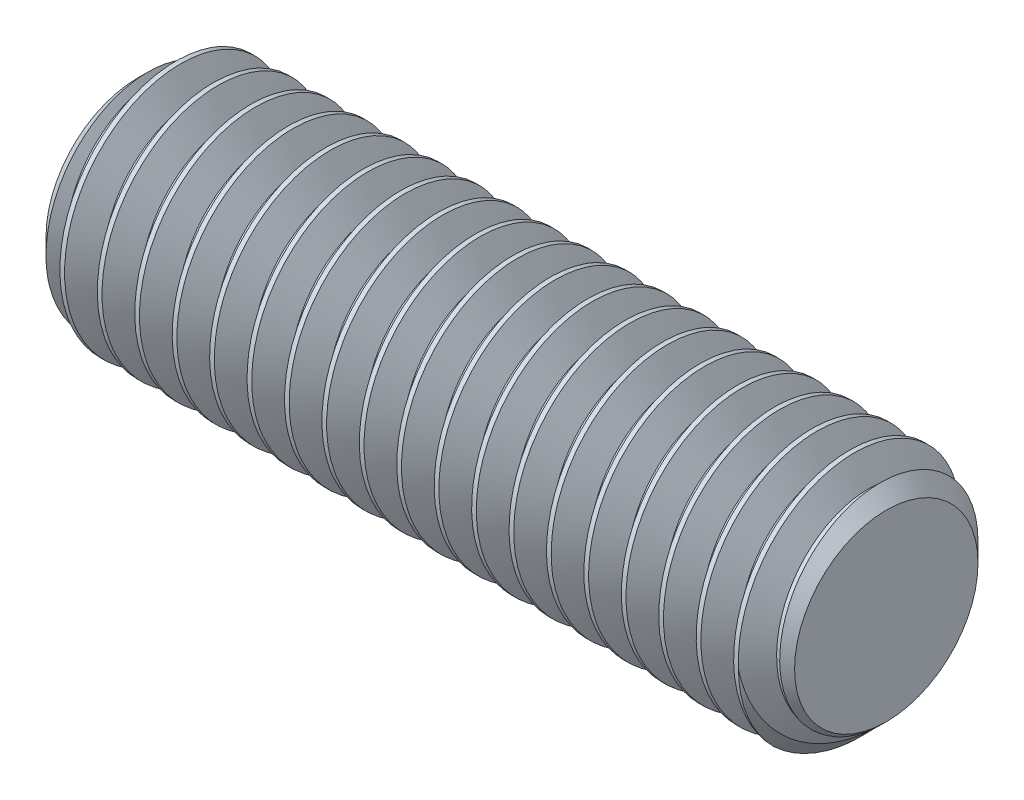
SolidWorks part; units mm, degrees
ref_plane "Front Plane" through (0, 0, 0) normal (0, 0, 1) x (1, 0, 0)
ref_plane "Top Plane" through (0, 0, 0) normal (0, 1, 0) x (1, 0, 0)
ref_plane "Right Plane" through (0, 0, 0) normal (1, 0, 0) x (0, 0, -1)
sketch "Sketch1" plane through (0, 0, 0) normal (0, 0, 1) x (1, 0, 0)
  line L0 (-12.5, 0) -> (12.5, 0) construction
  line L1 (12.5, 4) -> (12.5, -4) construction
  line L2 (-12.5, 4) -> (-12.5, -4) construction
  point P6 (8.125, -4)
  dimension "D1" = 4.375
  dimension "Thread Diameter" = 8
  dimension "Length" = 25
sketch "Sketch2" plane through (0, 0, 0) normal (1, 0, 0) x (0, 0, -1)
  circle A0 centre (0, 0) radius 4
extrude "Boss-Extrude1" add sketch "Sketch2" against normal up to vertex (12.5 mm away) and the other way up to vertex (12.5 mm away) up to point (-12.5, 0, 0) other way up to point (12.5, 0, 0)
sketch "Sketch3" plane through (12.5, 0, 0) normal (1, 0, 0) x (0, 0, -1)
  circle A1 centre (0, 0) radius 4
  circle A2 centre (0, 0) radius 4
  dimension "D1" = 0
curve "Helix/Spiral1" pitch 1.25 height 26.25 turns 21 parameters "Pitch"=1.25
chamfer "Chamfer1" distance 0.9375 angle 45 2 edges at (-12.5, 0, -4) (12.5, 0, -4)
sketch "Sketch4" plane through (0, 0, 0) normal (0, 0, 1) x (1, 0, 0)
  line L0 (12.4219, 4.1353) -> (13.0469, 3.0528) construction
  line L1 (13.0469, 3.0528) -> (13.6719, 4.1353) construction
  line L2 (13.6719, 4.1353) -> (12.4219, 4.1353) construction
  line L3 (13.0469, 4.1353) -> (13.0469, 4) construction
  line L4 (13.0469, 3.0528) -> (13.0469, 3.1881) construction
  line L5 (12.9687, 3.1881) -> (13.125, 3.1881) construction
  line L6 (12.5, 4) -> (13.5937, 4) construction
  line L7 (12.9687, 3.1881) -> (12.4609, 4.0677)
  line L8 (12.9687, 3.1881) -> (13.125, 3.1881)
  line L9 (12.4609, 4.0677) -> (13.6328, 4.0677)
  line L10 (13.6328, 4.0677) -> (13.125, 3.1881)
  point P13 (13.0469, 4.0677)
  dimension "D1" = 1.25
  dimension "D2" = 0.1562
sweep "Cut-Sweep3" cut profiles "Sketch4" path "Helix/Spiral1"
equation "\"D3@Helix/Spiral1\" = \"Length@Sketch1\"+\"Pitch@Helix/Spiral1\""
equation "\"D1@Chamfer1\" = \"Pitch@Helix/Spiral1\"*.75"
equation "\"D1@Sketch4\" = \"Pitch@Helix/Spiral1\""
equation "\"D2@Sketch4\" = \"D1@Sketch4\"/8"
equation "\"D1@Sketch1\" = \"Pitch@Helix/Spiral1\"*3.50"
